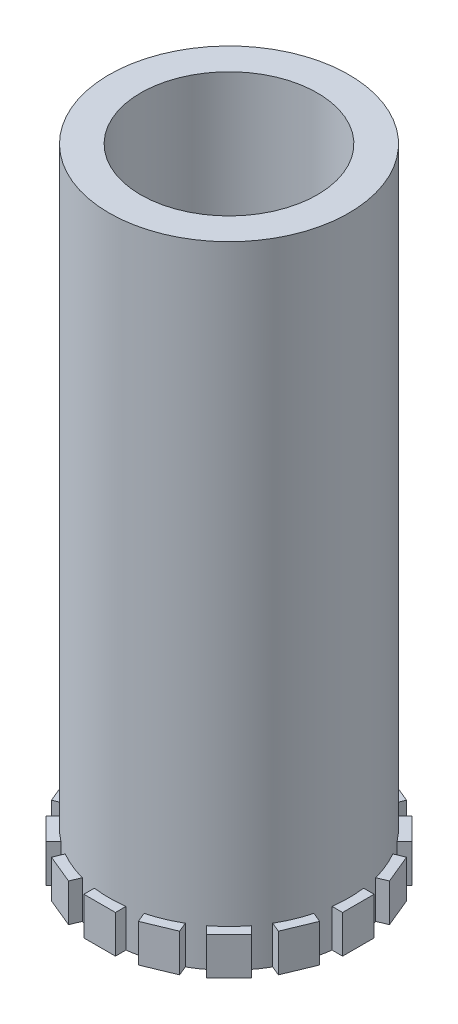
SolidWorks part; units mm, degrees
material "ABS"
ref_plane "前视基准面" through (0, 0, 0) normal (0, 0, 1) x (1, 0, 0)
ref_plane "上视基准面" through (0, 0, 0) normal (0, 1, 0) x (1, 0, 0)
ref_plane "右视基准面" through (0, 0, 0) normal (1, 0, 0) x (0, 0, -1)
sketch "草图1" plane through (0, 0, 0) normal (0, 1, 0) x (1, 0, 0)
  circle A0 centre (0, 0) radius 9.5
  circle A1 centre (0, 0) radius 7
  dimension "D1" = 19
  dimension "D2" = 14
extrude "凸台-拉伸1" add sketch "草图1" along normal blind 50
sketch "草图2" plane through (0, 0, 0) normal (0, -1, 0) x (-1, 0, 0)
  line L1 (10.25, -1.25) -> (8.75, -1.25)
  line L2 (10.25, -1.25) -> (10.25, 1.25)
  line L3 (10.25, 1.25) -> (8.75, 1.25)
  line L4 (8.75, -1.25) -> (8.75, 1.25)
  line L5 (10.25, -1.25) -> (8.75, 1.25) construction
  line L6 (10.25, 1.25) -> (8.75, -1.25) construction
  circle A0 centre (0, 0) radius 9.5 construction
  point P0 (9.5, 0)
  dimension "D1" = 1.5
  dimension "D2" = 2.5
extrude "凸台-拉伸2" add sketch "草图2" against normal blind 3
pattern_circular "阵列(圆周)1" count 16 over 360 about axis through (0, 50, 0) along (0, -1, 0) of "凸台-拉伸2"
